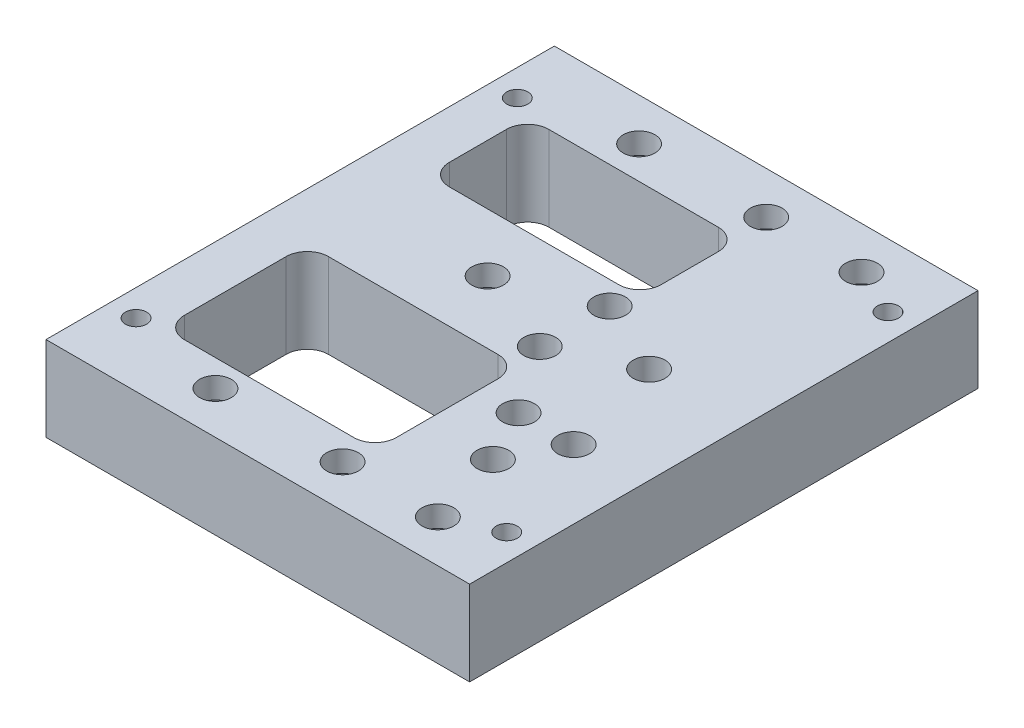
SolidWorks part; units mm, degrees
material "K110"
ref_plane "Front Plane" through (0, 0, 0) normal (0, 0, 1) x (1, 0, 0)
ref_plane "Top Plane" through (0, 0, 0) normal (0, 1, 0) x (1, 0, 0)
ref_plane "Right Plane" through (0, 0, 0) normal (1, 0, 0) x (0, 0, -1)
sketch "Sketch1" plane through (0, 0, 0) normal (0, 1, 0) x (1, 0, 0)
  line L1 (-100, -120) -> (100, -120)
  line L2 (-100, -120) -> (-100, 120)
  line L3 (-100, 120) -> (100, 120)
  line L4 (100, -120) -> (100, 120)
  line L5 (-100, -120) -> (100, 120) construction
  line L6 (-100, 120) -> (100, -120) construction
  point P0 (0, 0)
  dimension "D1" = 240
  dimension "D2" = 200
extrude "Boss-Extrude1" add sketch "Sketch1" against normal blind 40
sketch "Sketch2" plane through (0, 0, 0) normal (0, 1, 0) x (1, 0, 0)
  line L0 (-27.75, -63.53) -> (-27.75, -47.4) construction
  line L1 (-30.75, -44.4) -> (-34.75, -44.4) construction
  line L2 (-40.75, -38.4) -> (-40.75, -32.27) construction
  line L3 (-40.75, -32.27) -> (-59.87, -32.27) construction
  line L12 (-62.87, -35.27) -> (-62.87, -71.53) construction
  line L13 (-59.87, -74.53) -> (5.38, -74.53) construction
  line L14 (-15.75, -47.4) -> (-15.75, -63.53) construction
  line L15 (-8.75, -44.4) -> (-12.75, -44.4) construction
  line L16 (-2.75, -32.27) -> (-2.75, -38.4) construction
  line L17 (5.38, -32.27) -> (-2.75, -32.27) construction
  line L18 (8.38, -71.53) -> (8.38, -35.27) construction
  line L19 (-27.75, -63.53) -> (-27.75, -47.4)
  line L20 (-30.75, -44.4) -> (-34.75, -44.4)
  line L21 (-40.75, -38.4) -> (-40.75, -32.27)
  line L22 (-40.75, -32.27) -> (-59.87, -32.27)
  line L23 (-62.87, -35.27) -> (-62.87, -71.53)
  line L24 (-59.87, -74.53) -> (5.38, -74.53)
  line L25 (-15.75, -47.4) -> (-15.75, -63.53)
  line L26 (-8.75, -44.4) -> (-12.75, -44.4)
  line L27 (-2.75, -32.27) -> (-2.75, -38.4)
  line L28 (5.38, -32.27) -> (-2.75, -32.27)
  line L29 (8.38, -71.53) -> (8.38, -35.27)
  line L30 (-2.75, 47.73) -> (5.38, 47.73) construction
  line L31 (-2.75, 69.53) -> (-2.75, 47.73) construction
  line L32 (-40.75, 69.53) -> (-2.75, 69.53) construction
  line L33 (-40.75, 47.73) -> (-40.75, 69.53) construction
  line L34 (-59.87, 47.73) -> (-40.75, 47.73) construction
  line L35 (-62.87, 71.53) -> (-62.87, 50.73) construction
  line L36 (5.38, 74.53) -> (-59.87, 74.53) construction
  line L37 (8.38, 50.73) -> (8.38, 71.53) construction
  line L38 (-2.75, 47.73) -> (5.38, 47.73)
  line L39 (-2.75, 69.53) -> (-2.75, 47.73)
  line L40 (-40.75, 69.53) -> (-2.75, 69.53)
  line L41 (-40.75, 47.73) -> (-40.75, 69.53)
  line L42 (-59.87, 47.73) -> (-40.75, 47.73)
  line L43 (-62.87, 71.53) -> (-62.87, 50.73)
  line L44 (5.38, 74.53) -> (-59.87, 74.53)
  line L45 (8.38, 50.73) -> (8.38, 71.53)
  arc A0 (-27.75, -47.4) -> (-30.75, -44.4) centre (-30.75, -47.4) ccw construction
  arc A1 (-40.75, -38.4) -> (-34.75, -44.4) centre (-34.75, -38.4) ccw construction
  arc A2 (-59.87, -32.27) -> (-62.87, -35.27) centre (-59.87, -35.27) ccw construction
  arc A3 (-62.87, -71.53) -> (-59.87, -74.53) centre (-59.87, -71.53) ccw construction
  arc A4 (5.38, -74.53) -> (8.38, -71.53) centre (5.38, -71.53) ccw construction
  arc A5 (-27.75, -63.53) -> (-15.75, -63.53) centre (-21.75, -63.53) ccw construction
  arc A6 (-12.75, -44.4) -> (-15.75, -47.4) centre (-12.75, -47.4) ccw construction
  arc A7 (-8.75, -44.4) -> (-2.75, -38.4) centre (-8.75, -38.4) ccw construction
  arc A8 (8.38, -35.27) -> (5.38, -32.27) centre (5.38, -35.27) ccw construction
  arc A9 (-27.75, -47.4) -> (-30.75, -44.4) centre (-30.75, -47.4) ccw
  arc A10 (-40.75, -38.4) -> (-34.75, -44.4) centre (-34.75, -38.4) ccw
  arc A11 (-59.87, -32.27) -> (-62.87, -35.27) centre (-59.87, -35.27) ccw
  arc A12 (-62.87, -71.53) -> (-59.87, -74.53) centre (-59.87, -71.53) ccw
  arc A13 (5.38, -74.53) -> (8.38, -71.53) centre (5.38, -71.53) ccw
  arc A14 (-27.75, -63.53) -> (-15.75, -63.53) centre (-21.75, -63.53) ccw
  arc A15 (-12.75, -44.4) -> (-15.75, -47.4) centre (-12.75, -47.4) ccw
  arc A16 (-8.75, -44.4) -> (-2.75, -38.4) centre (-8.75, -38.4) ccw
  arc A17 (8.38, -35.27) -> (5.38, -32.27) centre (5.38, -35.27) ccw
  circle A18 centre (54.5, -63.53) radius 2.5 construction
  circle A19 centre (67.5, -38.4) radius 2.5 construction
  circle A20 centre (41.5, -38.4) radius 2.5 construction
  circle A21 centre (19.38, -6.27) radius 2.5 construction
  circle A22 centre (19.38, 26.73) radius 2.5 construction
  arc A23 (5.38, 47.73) -> (8.38, 50.73) centre (5.38, 50.73) ccw construction
  arc A24 (-62.87, 50.73) -> (-59.87, 47.73) centre (-59.87, 50.73) ccw construction
  arc A25 (-59.87, 74.53) -> (-62.87, 71.53) centre (-59.87, 71.53) ccw construction
  arc A26 (8.38, 71.53) -> (5.38, 74.53) centre (5.38, 71.53) ccw construction
  circle A27 centre (54.5, -63.53) radius 2.5
  circle A28 centre (67.5, -38.4) radius 2.5
  circle A29 centre (41.5, -38.4) radius 2.5
  circle A30 centre (19.38, -6.27) radius 2.5
  circle A31 centre (19.38, 26.73) radius 2.5
  arc A32 (5.38, 47.73) -> (8.38, 50.73) centre (5.38, 50.73) ccw
  arc A33 (-62.87, 50.73) -> (-59.87, 47.73) centre (-59.87, 50.73) ccw
  arc A34 (-59.87, 74.53) -> (-62.87, 71.53) centre (-59.87, 71.53) ccw
  arc A35 (8.38, 71.53) -> (5.38, 74.53) centre (5.38, 71.53) ccw
sketch "Sketch3" plane through (0, 0, 0) normal (0, 1, 0) x (1, 0, 0)
  line L1 (-67.245, 84.63) -> (12.755, 84.63)
  line L2 (-77.245, 74.63) -> (-77.245, 47.63)
  line L3 (-67.245, 37.63) -> (12.755, 37.63)
  line L4 (22.755, 74.63) -> (22.755, 47.63)
  line L8 (-62.87, -53.4) -> (8.38, -53.4) construction
  line L9 (-67.245, -19.4) -> (12.755, -19.4)
  line L10 (-77.245, -29.4) -> (-77.245, -77.4)
  line L11 (-67.245, -87.4) -> (12.755, -87.4)
  line L12 (22.755, -29.4) -> (22.755, -77.4)
  line L13 (-62.87, -35.27) -> (-62.87, -71.53) construction
  line L14 (8.38, -71.53) -> (8.38, -35.27) construction
  line L15 (-27.245, -74.53) -> (-27.245, -19.4) construction
  line L16 (-59.87, -74.53) -> (5.38, -74.53) construction
  line L17 (-27.245, 84.63) -> (-27.245, 47.73) construction
  line L18 (-62.87, 61.13) -> (8.38, 61.13) construction
  line L19 (-62.87, 71.53) -> (-62.87, 50.73) construction
  line L20 (8.38, 50.73) -> (8.38, 71.53) construction
  arc A0 (-77.245, 47.63) -> (-67.245, 37.63) centre (-67.245, 47.63) ccw
  arc A1 (12.755, 37.63) -> (22.755, 47.63) centre (12.755, 47.63) ccw
  arc A2 (22.755, 74.63) -> (12.755, 84.63) centre (12.755, 74.63) ccw
  arc A3 (-67.245, 84.63) -> (-77.245, 74.63) centre (-67.245, 74.63) ccw
  circle A4 centre (19.38, 26.73) radius 7.5
  circle A5 centre (19.38, -6.27) radius 7.5
  circle A6 centre (54.5, -63.53) radius 7.5
  circle A7 centre (67.5, -38.4) radius 7.5
  circle A8 centre (41.5, -38.4) radius 7.5
  arc A9 (-77.245, -77.4) -> (-67.245, -87.4) centre (-67.245, -77.4) ccw
  arc A10 (12.755, -87.4) -> (22.755, -77.4) centre (12.755, -77.4) ccw
  arc A11 (22.755, -29.4) -> (12.755, -19.4) centre (12.755, -29.4) ccw
  arc A12 (-67.245, -19.4) -> (-77.245, -29.4) centre (-67.245, -29.4) ccw
  dimension "D5" = 10
  dimension "D6" = 15
  dimension "D11" = 10
  dimension "D2" = 100
  dimension "D3" = 47
  dimension "D7" = 68
  dimension "D8" = 100
extrude "Cut-Extrude2" cut sketch "Sketch3" against normal up to next
sketch "Sketch4" plane through (0, -40, 0) normal (0, -1, 0) x (1, 0, 0)
  circle A0 centre (19.38, -26.73) radius 9
  circle A1 centre (19.38, 6.27) radius 9
  circle A2 centre (41.5, 38.4) radius 9
  circle A3 centre (67.5, 38.4) radius 9
  circle A4 centre (54.5, 63.53) radius 9
  dimension "D1" = 18
extrude "Cut-Extrude3" cut sketch "Sketch4" against normal blind 5
extrude "Cut-Extrude9" cut sketch "Sketch11" against normal through all
sketch "Sketch11" plane through (89.63, 0, 0) normal (0, 1, 0) x (1, 0, 0)
  circle A0 centre (-35.13, 10.23) radius 7.5
  circle A1 centre (-111.38, 10.23) radius 7.5
extrude "Cut-Extrude10" cut sketch "Sketch12" against normal blind 5
sketch "Sketch12" plane through (89.63, -40, 0) normal (0, -1, 0) x (1, 0, 0)
  circle A0 centre (-35.13, -10.23) radius 10
extrude "Cut-Extrude11" cut sketch "Sketch13" against normal blind 30
sketch "Sketch13" plane through (89.63, -40, 0) normal (0, -1, 0) x (1, 0, 0)
  circle A0 centre (-111.38, -10.23) radius 10
hole_wizard "M10 Tapped Hole1" positions "Sketch27" profile "Sketch15" tap size "M10" standard "ISO"
sketch "Sketch27" plane through (0, -40, 0) normal (0, -1, 0) x (-1, 0, 0)
  line L0 (-100, -120) -> (-100, 120) construction
  line L1 (-100, 120) -> (100, 120) construction
  line L2 (100, 120) -> (100, -120) construction
  line L3 (100, -120) -> (-100, -120) construction
  point P0 (-87.5, 107.5)
  point P2 (87.5, 107.5)
  point P4 (87.5, -107.5)
  point P6 (-87.5, -107.5)
  point P21 (0, 0)
  dimension "D1" = 12.5
  dimension "D2" = 12.5
  dimension "D3" = 12.5
  dimension "D4" = 12.5
sketch "Sketch15" plane through (87.5, -40, -107.5) normal (1, 0, 0) x (0, 0, -1)
  line L0 (0, 0) -> (0, 30.0537)
  line L1 (0, 30.0537) -> (4.25, 27.5)
  line L2 (4.25, 27.5) -> (4.25, 0.775)
  line L3 (4.25, 0.775) -> (5.025, 0)
  line L5 (5.025, 0) -> (0, 0)
  line L6 (-4.25, 0.775) -> (-5.025, 0) construction
  line L10 (0, 30.0537) -> (-4.25, 27.5) construction
  line L11 (0, -6.35) -> (0, 107.95) construction
  dimension "Tap Drill Dia." = 8.5
  dimension "Tap Drill Depth" = 27.5
  dimension "Near C'Sink Dia." = 10.05
  dimension "Near C'Sink Angle" = 90
  dimension "Drill Angle" = 118
cosmetic thread "Hole Thread1" parameters "D1"=20, "D2"=10
cosmetic thread "Hole Thread2" parameters "D1"=20, "D2"=10
cosmetic thread "Hole Thread3" parameters "D1"=20, "D2"=10
cosmetic thread "Hole Thread4" parameters "D1"=20, "D2"=10
hole_wizard "Ø10.0mm Dowel Hole2" positions "Sketch26" profile "Sketch25" hole size "Ø10.0" standard "ISO" end condition through all
sketch "Sketch26" plane through (0, -40, 0) normal (0, -1, 0) x (-1, 0, 0)
  line L0 (-100, -120) -> (-100, 120) construction
  line L1 (100, 120) -> (100, -120) construction
  circle A0 centre (-87.5, 107.5) radius 4.25 construction
  circle A1 centre (-87.5, -107.5) radius 4.25 construction
  point P0 (-87.5, 90)
  point P2 (87.5, 90)
  point P4 (87.5, -90)
  point P6 (-87.5, -90)
  dimension "D4" = 17.5
  dimension "D1" = 12.5
  dimension "D2" = 17.5
  dimension "D3" = 12.5
sketch "Sketch25" plane through (87.5, -40, -90) normal (1, 0, 0) x (0, 0, -1)
  line L0 (0, 0) -> (0, 40)
  line L1 (0, 40) -> (5, 40)
  line L2 (5, 40) -> (5, 0)
  line L5 (5, 0) -> (0, 0)
  line L11 (0, -6.35) -> (0, 107.95) construction
  dimension "Thru Hole Dia." = 10
  dimension "Thru Hole Depth" = 40
sketch "Sketch28" plane through (0, 0, 0) normal (0, 1, 0) x (1, 0, 0)
  line L0 (-372.87, -95) -> (89.63, -95) construction
  line L2 (100, -120) -> (100, 120) construction
  circle A0 centre (20, -100) radius 7.5
  circle A1 centre (65, -100) radius 7.5
  circle A4 centre (-40, -100) radius 7.5
  point P10 (0, 0)
  point P12 (0, 0)
  point P16 (79.0935, -110.5265)
  dimension "D1" = 15
  dimension "D2" = 5
  dimension "D3" = 60
  dimension "D4" = 35
  dimension "D5" = 45
extrude "Cut-Extrude12" cut sketch "Sketch28" against normal up to next
mirror "Mirror1" about plane through (0, 0, 0) normal (0, 0, 1) of "Cut-Extrude12"
sketch "Sketch29" plane through (0, -40, 0) normal (0, -1, 0) x (1, 0, 0)
  circle A0 centre (-40, 100) radius 9
  circle A1 centre (20, 100) radius 9
  circle A2 centre (20, -100) radius 9
  circle A3 centre (-40, -100) radius 9
  circle A4 centre (65, 100) radius 9
  circle A5 centre (65, -100) radius 9
  dimension "D1" = 18
extrude "Cut-Extrude13" cut sketch "Sketch29" against normal blind 30
